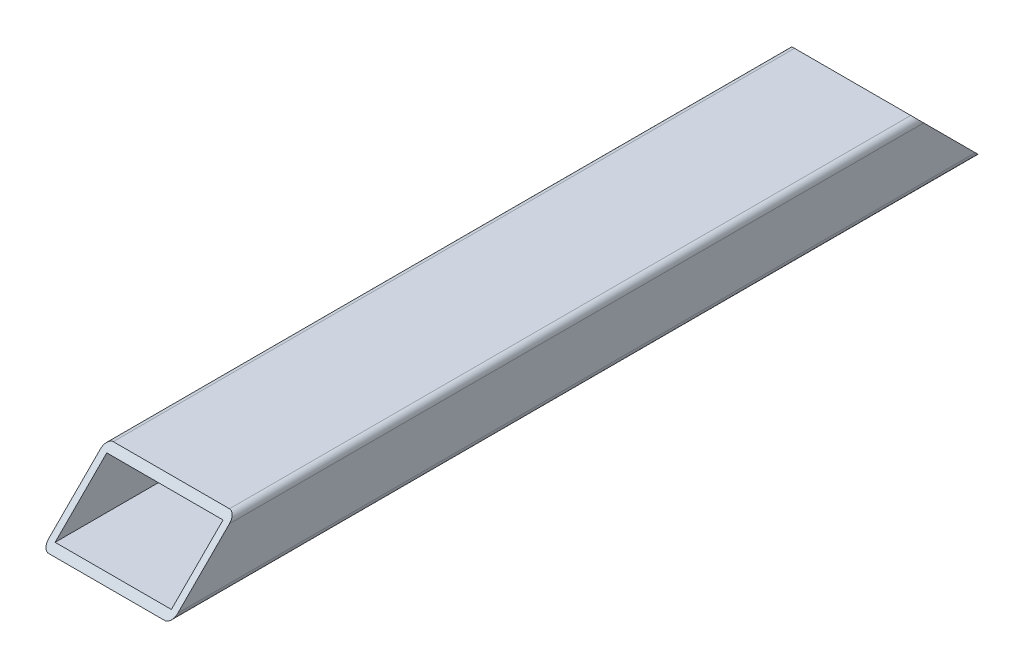
SolidWorks part; units mm, degrees
material "1.4003 (X2CrNi12)"
ref_plane "Ön Düzlem" through (0, 0, 0) normal (0, 0, 1) x (1, 0, 0)
ref_plane "Üst Düzlem" through (0, 0, 0) normal (0, 1, 0) x (1, 0, 0)
ref_plane "Sağ Düzlem" through (0, 0, 0) normal (1, 0, 0) x (0, 0, -1)
sketch "Çizim1" plane through (0, 0, 0) normal (0, 0, 1) x (1, 0, 0)
  line L0 (-36, 16) -> (-36, -16)
  line L1 (-36, 20) -> (36, 20)
  line L2 (-40, 16) -> (-40, -16)
  line L3 (-36, -20) -> (36, -20)
  line L4 (40, 16) -> (40, -16)
  line L5 (-40, 20) -> (40, -20) construction
  line L6 (-40, -20) -> (40, 20) construction
  line L7 (-36, -16) -> (36, -16)
  line L8 (36, 16) -> (36, -16)
  line L9 (-36, 16) -> (36, 16)
  line L10 (-40, 20) -> (40, 20) construction
  line L11 (40, 20) -> (40, -20) construction
  line L12 (-40, -20) -> (40, -20) construction
  line L13 (-40, 20) -> (-40, -20) construction
  arc A0 (36, 20) -> (40, 16) centre (36, 16) cw
  arc A1 (40, -16) -> (36, -20) centre (36, -16) cw
  arc A2 (-40, -16) -> (-36, -20) centre (-36, -16) ccw
  arc A3 (-36, 20) -> (-40, 16) centre (-36, 16) ccw
  point P0 (0, 0)
  dimension "D4" = 4
  dimension "D1" = 80
  dimension "D2" = 40
  dimension "D3" = 4
extrude "Yükseklik-Ekstrüzyon1" add sketch "Çizim1" along normal blind 251 and the other way blind 251
sketch "Çizim2" plane through (0, 0, 0) normal (1, 0, 0) x (0, 0, -1)
  line L7 (-251, 20) -> (-211, 20)
  line L8 (251, 20) -> (-251, 20) construction
  line L9 (-211, 20) -> (-251, -20)
  line L10 (-251, -20) -> (-251, 20)
  line L11 (251, -20) -> (211, 20)
  line L12 (211, 20) -> (251, 20)
  line L13 (251, 20) -> (251, -20)
  dimension "D1" = 45
  dimension "D2" = 45
extrude "Kes-Ekstrüzyon1" cut sketch "Çizim2" against normal blind 86 and the other way blind 75
